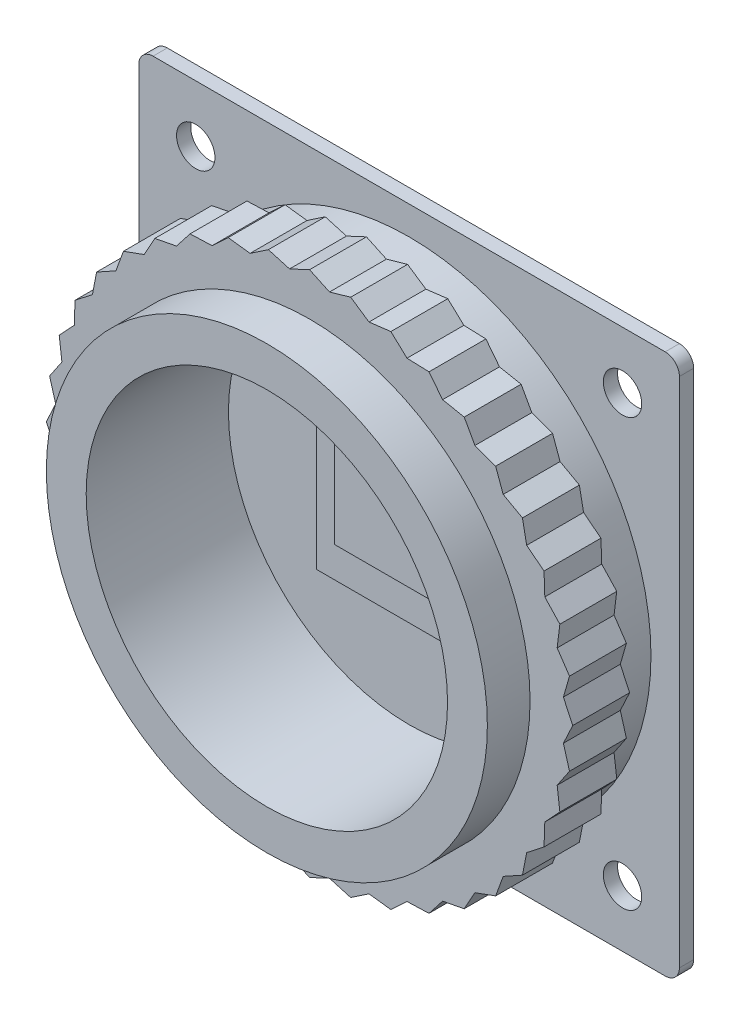
SolidWorks part; units mm, degrees
ref_plane "Front Plane" through (0, 0, 0) normal (0, 0, 1) x (1, 0, 0)
ref_plane "Top Plane" through (0, 0, 0) normal (0, 1, 0) x (1, 0, 0)
ref_plane "Right Plane" through (0, 0, 0) normal (1, 0, 0) x (0, 0, -1)
sketch "Sketch1" plane through (0, 0, 0) normal (0, 0, 1) x (1, 0, 0)
  line L0 (1, 0) -> (37, 0)
  line L1 (38, 1) -> (38, 37)
  line L2 (37, 38) -> (1, 38)
  line L3 (0, 37) -> (0, 1)
  arc A0 (37, 0) -> (38, 1) centre (37, 1) ccw
  arc A1 (38, 37) -> (37, 38) centre (37, 37) ccw
  arc A2 (1, 38) -> (0, 37) centre (1, 37) ccw
  arc A3 (0, 1) -> (1, 0) centre (1, 1) ccw
extrude "PCB" add sketch "Sketch1" along normal blind 1
ref_plane "Plane_z1" through (0, 0, 1) normal (0, 0, 1) x (1, 0, 0)
sketch "Sketch2" plane through (0, 0, 1) normal (0, 0, 1) x (1, 0, 0)
  line L1 (13.5, 13.5) -> (24.5, 13.5)
  line L2 (13.5, 13.5) -> (13.5, 24.5)
  line L3 (13.5, 24.5) -> (24.5, 24.5)
  line L4 (24.5, 13.5) -> (24.5, 24.5)
extrude "Sensor" add sketch "Sketch2" along normal blind 1
ref_plane "Plane_z2" through (0, 0, 2) normal (0, 0, 1) x (1, 0, 0)
sketch "Sketch3" plane through (0, 0, 2) normal (0, 0, 1) x (1, 0, 0)
  line L1 (15.05, 15.95) -> (22.95, 15.95)
  line L2 (15.05, 15.95) -> (15.05, 22.05)
  line L3 (15.05, 22.05) -> (22.95, 22.05)
  line L4 (22.95, 15.95) -> (22.95, 22.05)
extrude "Sensor_glass" add sketch "Sketch3" along normal blind 0.3
sketch "Sketch4" plane through (0, 0, 1) normal (0, 0, 1) x (1, 0, 0)
  circle A0 centre (19, 19) radius 17
  circle A1 centre (19, 19) radius 12.7
extrude "Mount_base" add sketch "Sketch4" along normal blind 3
ref_plane "Plane_z4" through (0, 0, 4) normal (0, 0, 1) x (1, 0, 0)
sketch "Sketch5" plane through (0, 0, 4) normal (0, 0, 1) x (1, 0, 0)
  line L0 (37.5, 19) -> (36.8448, 20.4044)
  line L1 (36.8448, 20.4044) -> (37.2722, 21.894)
  line L2 (37.2722, 21.894) -> (36.4054, 23.1787)
  line L3 (36.4054, 23.1787) -> (36.5945, 24.7168)
  line L4 (36.5945, 24.7168) -> (35.5374, 25.85)
  line L5 (35.5374, 25.85) -> (35.4836, 27.3988)
  line L6 (35.4836, 27.3988) -> (34.2623, 28.3527)
  line L7 (34.2623, 28.3527) -> (33.9668, 29.874)
  line L8 (33.9668, 29.874) -> (32.6113, 30.6251)
  line L9 (32.6113, 30.6251) -> (32.0815, 32.0815)
  line L10 (32.0815, 32.0815) -> (30.6251, 32.6113)
  line L11 (30.6251, 32.6113) -> (29.874, 33.9668)
  line L12 (29.874, 33.9668) -> (28.3527, 34.2623)
  line L13 (28.3527, 34.2623) -> (27.3988, 35.4836)
  line L14 (27.3988, 35.4836) -> (25.85, 35.5374)
  line L15 (25.85, 35.5374) -> (24.7168, 36.5945)
  line L16 (24.7168, 36.5945) -> (23.1787, 36.4054)
  line L17 (23.1787, 36.4054) -> (21.894, 37.2722)
  line L18 (21.894, 37.2722) -> (20.4044, 36.8448)
  line L19 (20.4044, 36.8448) -> (19, 37.5)
  line L20 (19, 37.5) -> (17.5956, 36.8448)
  line L21 (17.5956, 36.8448) -> (16.106, 37.2722)
  line L22 (16.106, 37.2722) -> (14.8213, 36.4054)
  line L23 (14.8213, 36.4054) -> (13.2832, 36.5945)
  line L24 (13.2832, 36.5945) -> (12.15, 35.5374)
  line L25 (12.15, 35.5374) -> (10.6012, 35.4836)
  line L26 (10.6012, 35.4836) -> (9.6473, 34.2623)
  line L27 (9.6473, 34.2623) -> (8.126, 33.9668)
  line L28 (8.126, 33.9668) -> (7.3749, 32.6113)
  line L29 (7.3749, 32.6113) -> (5.9185, 32.0815)
  line L30 (5.9185, 32.0815) -> (5.3887, 30.6251)
  line L31 (5.3887, 30.6251) -> (4.0332, 29.874)
  line L32 (4.0332, 29.874) -> (3.7377, 28.3527)
  line L33 (3.7377, 28.3527) -> (2.5164, 27.3988)
  line L34 (2.5164, 27.3988) -> (2.4626, 25.85)
  line L35 (2.4626, 25.85) -> (1.4055, 24.7168)
  line L36 (1.4055, 24.7168) -> (1.5946, 23.1787)
  line L37 (1.5946, 23.1787) -> (0.7278, 21.894)
  line L38 (0.7278, 21.894) -> (1.1552, 20.4044)
  line L39 (1.1552, 20.4044) -> (0.5, 19)
  line L40 (0.5, 19) -> (1.1552, 17.5956)
  line L41 (1.1552, 17.5956) -> (0.7278, 16.106)
  line L42 (0.7278, 16.106) -> (1.5946, 14.8213)
  line L43 (1.5946, 14.8213) -> (1.4055, 13.2832)
  line L44 (1.4055, 13.2832) -> (2.4626, 12.15)
  line L45 (2.4626, 12.15) -> (2.5164, 10.6012)
  line L46 (2.5164, 10.6012) -> (3.7377, 9.6473)
  line L47 (3.7377, 9.6473) -> (4.0332, 8.126)
  line L48 (4.0332, 8.126) -> (5.3887, 7.3749)
  line L49 (5.3887, 7.3749) -> (5.9185, 5.9185)
  line L50 (5.9185, 5.9185) -> (7.3749, 5.3887)
  line L51 (7.3749, 5.3887) -> (8.126, 4.0332)
  line L52 (8.126, 4.0332) -> (9.6473, 3.7377)
  line L53 (9.6473, 3.7377) -> (10.6012, 2.5164)
  line L54 (10.6012, 2.5164) -> (12.15, 2.4626)
  line L55 (12.15, 2.4626) -> (13.2832, 1.4055)
  line L56 (13.2832, 1.4055) -> (14.8213, 1.5946)
  line L57 (14.8213, 1.5946) -> (16.106, 0.7278)
  line L58 (16.106, 0.7278) -> (17.5956, 1.1552)
  line L59 (17.5956, 1.1552) -> (19, 0.5)
  line L60 (19, 0.5) -> (20.4044, 1.1552)
  line L61 (20.4044, 1.1552) -> (21.894, 0.7278)
  line L62 (21.894, 0.7278) -> (23.1787, 1.5946)
  line L63 (23.1787, 1.5946) -> (24.7168, 1.4055)
  line L64 (24.7168, 1.4055) -> (25.85, 2.4626)
  line L65 (25.85, 2.4626) -> (27.3988, 2.5164)
  line L66 (27.3988, 2.5164) -> (28.3527, 3.7377)
  line L67 (28.3527, 3.7377) -> (29.874, 4.0332)
  line L68 (29.874, 4.0332) -> (30.6251, 5.3887)
  line L69 (30.6251, 5.3887) -> (32.0815, 5.9185)
  line L70 (32.0815, 5.9185) -> (32.6113, 7.3749)
  line L71 (32.6113, 7.3749) -> (33.9668, 8.126)
  line L72 (33.9668, 8.126) -> (34.2623, 9.6473)
  line L73 (34.2623, 9.6473) -> (35.4836, 10.6012)
  line L74 (35.4836, 10.6012) -> (35.5374, 12.15)
  line L75 (35.5374, 12.15) -> (36.5945, 13.2832)
  line L76 (36.5945, 13.2832) -> (36.4054, 14.8213)
  line L77 (36.4054, 14.8213) -> (37.2722, 16.106)
  line L78 (37.2722, 16.106) -> (36.8448, 17.5956)
  line L79 (36.8448, 17.5956) -> (37.5, 19)
  circle A0 centre (19, 19) radius 12.7
extrude "Lock_ring" add sketch "Sketch5" along normal blind 4
ref_plane "Plane_z8" through (0, 0, 8) normal (0, 0, 1) x (1, 0, 0)
sketch "Sketch6" plane through (0, 0, 8) normal (0, 0, 1) x (1, 0, 0)
  circle A0 centre (19, 19) radius 15.5
  circle A1 centre (19, 19) radius 12.7
extrude "CS_tube" add sketch "Sketch6" along normal blind 3
sketch "Sketch7" plane through (0, 0, 0) normal (0, 0, 1) x (1, 0, 0)
  line L1 (8.5, 0.75) -> (29.5, 0.75)
  line L2 (8.5, 0.75) -> (8.5, 6.25)
  line L3 (8.5, 6.25) -> (29.5, 6.25)
  line L4 (29.5, 0.75) -> (29.5, 6.25)
extrude "FFC_connector" add sketch "Sketch7" against normal blind 2.5
sketch "Sketch8" plane through (0, 0, 1) normal (0, 0, 1) x (1, 0, 0)
  circle A0 centre (4, 4) radius 1.35
  circle A1 centre (4, 34) radius 1.35
  circle A2 centre (34, 4) radius 1.35
  circle A3 centre (34, 34) radius 1.35
extrude "Holes" cut sketch "Sketch8" against normal blind 1
equation "\"pcb_t\" = 1.0mm"
equation "\"D1@PCB\" = \"pcb_t\""
